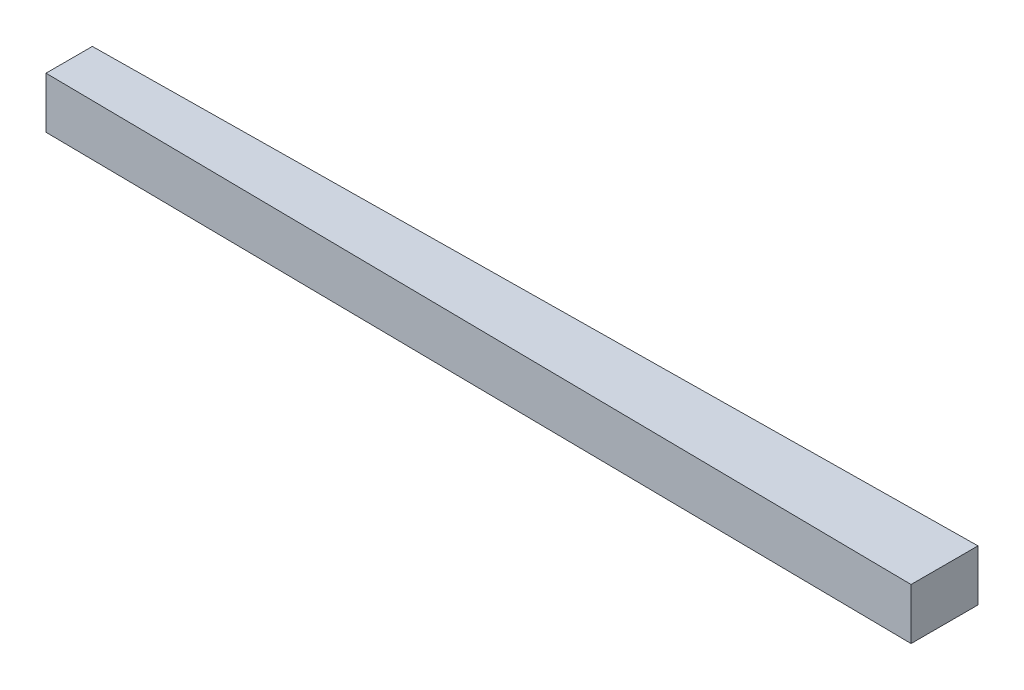
SolidWorks part; units mm, degrees
material "1023 Carbon Steel Sheet (SS)"
ref_plane "Front Plane" through (0, 0, 0) normal (0, 0, 1) x (1, 0, 0)
ref_plane "Top Plane" through (0, 0, 0) normal (0, 1, 0) x (1, 0, 0)
ref_plane "Right Plane" through (0, 0, 0) normal (1, 0, 0) x (0, 0, -1)
sketch "Sketch1" plane through (0, 0, 0) normal (0, 1, 0) x (1, 0, 0)
  line L0 (-42.5, 0) -> (42.5, 0) construction
  line L4 (-42.5, -2.25) -> (-42.5, 2.25)
  line L5 (-42.5, 2.25) -> (42.5, 3.25)
  line L6 (42.5, 3.25) -> (42.5, -3.25)
  line L7 (-42.5, -2.25) -> (42.5, -3.25)
  point P2 (0, 0)
  dimension "D1" = 85
  dimension "D2" = 2.25
  dimension "D3" = 3.25
extrude "Boss-Extrude1" add sketch "Sketch1" along normal blind 4.97
